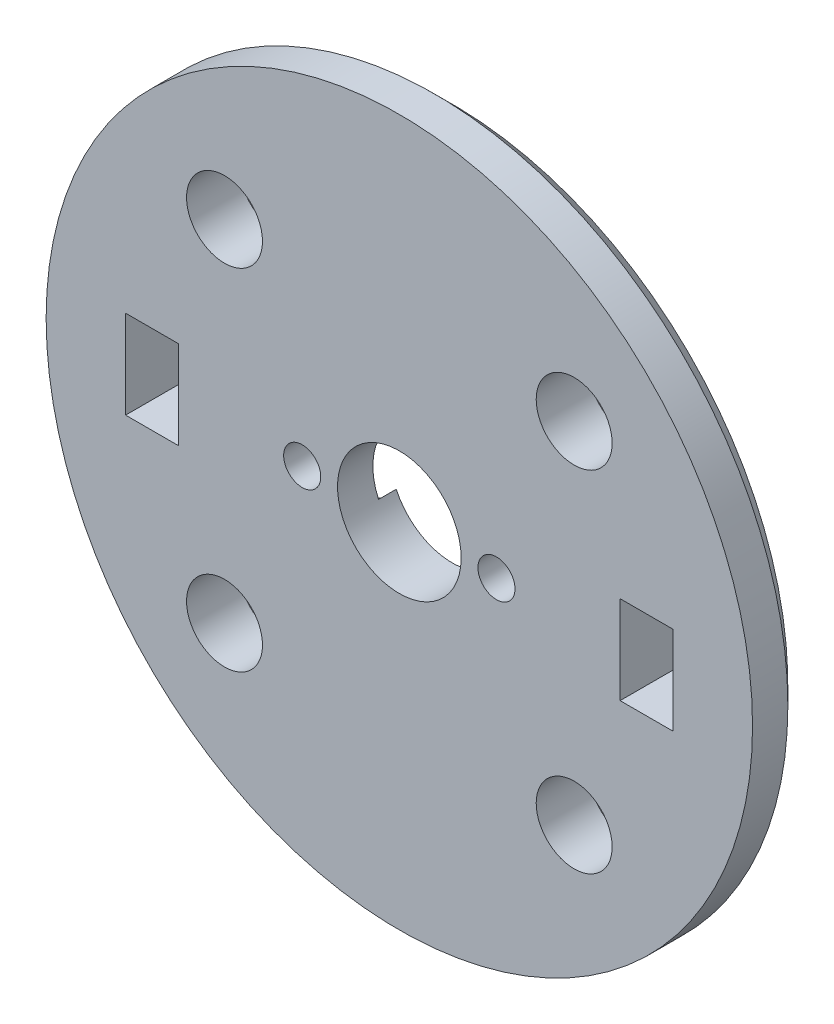
SolidWorks part; units mm, degrees
ref_plane "前视基准面" through (0, 0, 0) normal (0, 0, 1) x (1, 0, 0)
ref_plane "上视基准面" through (0, 0, 0) normal (0, 1, 0) x (1, 0, 0)
ref_plane "右视基准面" through (0, 0, 0) normal (1, 0, 0) x (0, 0, -1)
sketch "草图1" plane through (0, 0, 0) normal (0, 0, 1) x (1, 0, 0)
  circle A0 centre (0, 0) radius 20
  dimension "D1" = 40
extrude "凸台-拉伸1" add sketch "草图1" along normal blind 2
sketch "草图2" plane through (0, 0, 2) normal (0, 0, 1) x (1, 0, 0)
  circle A0 centre (0, 0) radius 3.5
  dimension "D1" = 7
extrude "切除-拉伸1" cut sketch "草图2" against normal blind 2
sketch "草图3" plane through (0, 0, 2) normal (0, 0, 1) x (1, 0, 0)
  circle A0 centre (-5.5, 0) radius 1.05
  circle A1 centre (5.5, 0) radius 1.05
  circle A2 centre (0, 0) radius 3.5 construction
  dimension "D1" = 2.1
  dimension "D2" = 2.1
  dimension "D3" = 11
  dimension "D4" = 5.5
  dimension "D5" = 5.5
extrude "切除-拉伸2" cut sketch "草图3" against normal blind 2
sketch "草图4" plane through (0, 0, 2) normal (0, 0, 1) x (1, 0, 0)
  circle A0 centre (0, 0) radius 7.7
  circle A1 centre (0, 0) radius 10
  dimension "D1" = 15.4
  dimension "D2" = 20
extrude "凸台-拉伸2" [suppressed] add sketch "草图4" along normal blind 10
sketch "草图5" plane through (0, 0, 0) normal (0, 0, -1) x (-1, 0, 0)
  circle A0 centre (0, 0) radius 20
  circle A1 centre (0, 0) radius 8.25
  dimension "D1" = 16.5
extrude "凸台-拉伸3" add sketch "草图5" along normal blind 1
sketch "草图6" plane through (0, 0, -1) normal (0, 0, -1) x (-1, 0, 0)
  circle A0 centre (0, 0) radius 14
  circle A1 centre (0, 0) radius 12
  circle A2 centre (0, 0) radius 16
  dimension "D1" = 28
  dimension "D2" = 24
  dimension "D3" = 32
sketch "草图7" [suppressed] plane through (0, 0, -1) normal (0, 0, -1) x (-1, 0, 0)
  circle A0 centre (0, 0) radius 11.25
  circle A1 centre (0, 0) radius 8.5
  dimension "D1" = 22.5
  dimension "D2" = 17
sketch "草图8" plane through (0, 0, 0) normal (0, 0, -1) x (-1, 0, 0)
  circle A0 centre (0, 0) radius 8.25
  arc A1 (-3.1761, -1.4704) -> (3.1761, -1.4704) centre (0, 0) ccw
  arc A2 (-3.1761, 1.4704) -> (-3.1761, -1.4704) centre (-5.5, 0) ccw
  arc A3 (3.1761, -1.4704) -> (3.1761, 1.4704) centre (5.5, 0) ccw
  arc A4 (3.1761, 1.4704) -> (-3.1761, 1.4704) centre (0, 0) ccw
  circle M1 centre (0, 0) radius 3.5
  circle M4 centre (0, 0) radius 8.25
  dimension "D1" = 16.5
extrude "凸台-拉伸4" add sketch "草图8" along normal blind 1 contours A3 A2 M1 M4 | A3 A0 A2 M1
sketch "草图9" plane through (0, 0, -1) normal (0, 0, -1) x (-1, 0, 0)
  circle A0 centre (0, 0) radius 10.2
  circle A2 centre (0, 0) radius 7
  dimension "D1" = 20.4
  dimension "D2" = 14
extrude "切除-拉伸3" cut sketch "草图9" against normal blind 1.6
sketch "草图11" [suppressed] plane through (0, 0, 0.6) normal (0, 0, -1) x (-1, 0, 0)
  circle A0 centre (0, 0) radius 8.3
  circle A1 centre (0, 0) radius 11.5
  circle A2 centre (0, 0) radius 11.5
  dimension "D1" = 0
sketch "草图12" plane through (0, 0, 0.6) normal (0, 0, -1) x (-1, 0, 0)
  line L0 (6.3442, 2.9583) -> (9.2443, 4.3107)
  line L1 (6.3442, -2.9583) -> (9.2443, -4.3107)
  arc A0 (6.3442, 2.9583) -> (6.3442, -2.9583) centre (0, 0) cw
  circle A1 centre (0, 0) radius 7 construction
  arc A2 (9.2443, -4.3107) -> (9.2443, 4.3107) centre (0, 0) ccw
  circle A3 centre (0, 0) radius 10.2 construction
  dimension "D1" = 50
  dimension "D2" = 50
extrude "凸台-拉伸5" add sketch "草图12" along normal blind 1.6
pattern_circular "阵列(圆周)2" count 2 over 180 about axis through (0, 0, 0) along (0, 0, 1) of "凸台-拉伸5"
sketch "草图13" plane through (0, 0, 0) normal (0, 0, -1) x (-1, 0, 0)
  circle A0 centre (5.5, 0) radius 2.75
  circle A1 centre (-5.5, 0) radius 2.75
  dimension "D1" = 5.5
  dimension "D2" = 5.5
extrude "切除-拉伸4" cut sketch "草图13" along normal blind 1.6
fillet "圆角1" radius 1.5 8 edges at (9.2443, -4.3107, -0.2) (-9.2443, -4.3107, -0.2) (-6.3442, -2.9583, -0.2) (6.3442, -2.9583, -0.2) (9.2443, 4.3107, -0.2) (6.3442, 2.9583, -0.2) (-9.2443, 4.3107, -0.2) (-6.3442, 2.9583, -0.2)
sketch "草图14" plane through (0, 0, -1) normal (0, 0, -1) x (-1, 0, 0)
  line L0 (0, 0) -> (20, 0) construction
  line L1 (0, 0) -> (14.1421, -14.1421) construction
  circle A0 centre (9.8995, -9.8995) radius 2.15
  circle A1 centre (0, 0) radius 14 construction
  circle A2 centre (-9.8995, -9.8995) radius 2.15
  circle A3 centre (-9.8995, 9.8995) radius 2.15
  circle A4 centre (9.8995, 9.8995) radius 2.15
  point P19 (0, 0)
  dimension "D2" = 0
  dimension "D3" = 4.3
  dimension "D1" = 45
  dimension "D4" = 4
extrude "切除-拉伸5" cut sketch "草图14" against normal blind 10
sketch "草图15" plane through (0, 0, 2) normal (0, 0, 1) x (1, 0, 0)
  line L0 (0, 0) -> (29.4349, 0) construction
  line L1 (-12.5, -2.5) -> (-12.5, 2.5)
  line L2 (12.5, 2.5) -> (15.5, 2.5)
  line L3 (12.5, 2.5) -> (12.5, -2.5)
  line L4 (12.5, -2.5) -> (15.5, -2.5)
  line L5 (15.5, 2.5) -> (15.5, -2.5)
  line L6 (12.5, 2.5) -> (15.5, -2.5) construction
  line L7 (12.5, -2.5) -> (15.5, 2.5) construction
  line L8 (-12.5, -2.5) -> (-15.5, -2.5)
  line L9 (-15.5, -2.5) -> (-15.5, 2.5)
  line L10 (-12.5, 2.5) -> (-15.5, 2.5)
  circle A0 centre (0, 0) radius 14 construction
  point P1 (14, 0)
  point P16 (0, 0)
  dimension "D1" = 3
  dimension "D2" = 5
  dimension "D3" = 2
extrude "切除-拉伸6" cut sketch "草图15" against normal blind 10
sketch "草图16" [suppressed] plane through (0, 0, 2) normal (0, 0, 1) x (1, 0, 0)
  circle A1 centre (0, 0) radius 20
  circle A2 centre (0, 0) radius 20
  dimension "D1" = 0
sketch "草图17" [suppressed] plane through (0, 0, -1) normal (0, 0, -1) x (-1, 0, 0)
  circle A0 centre (0, 0) radius 20
  circle A1 centre (0, 0) radius 18
  dimension "D1" = 40
  dimension "D2" = 36
chamfer "倒角1" distance 1 angle 45 1 edges at (-20, 0, -1)
